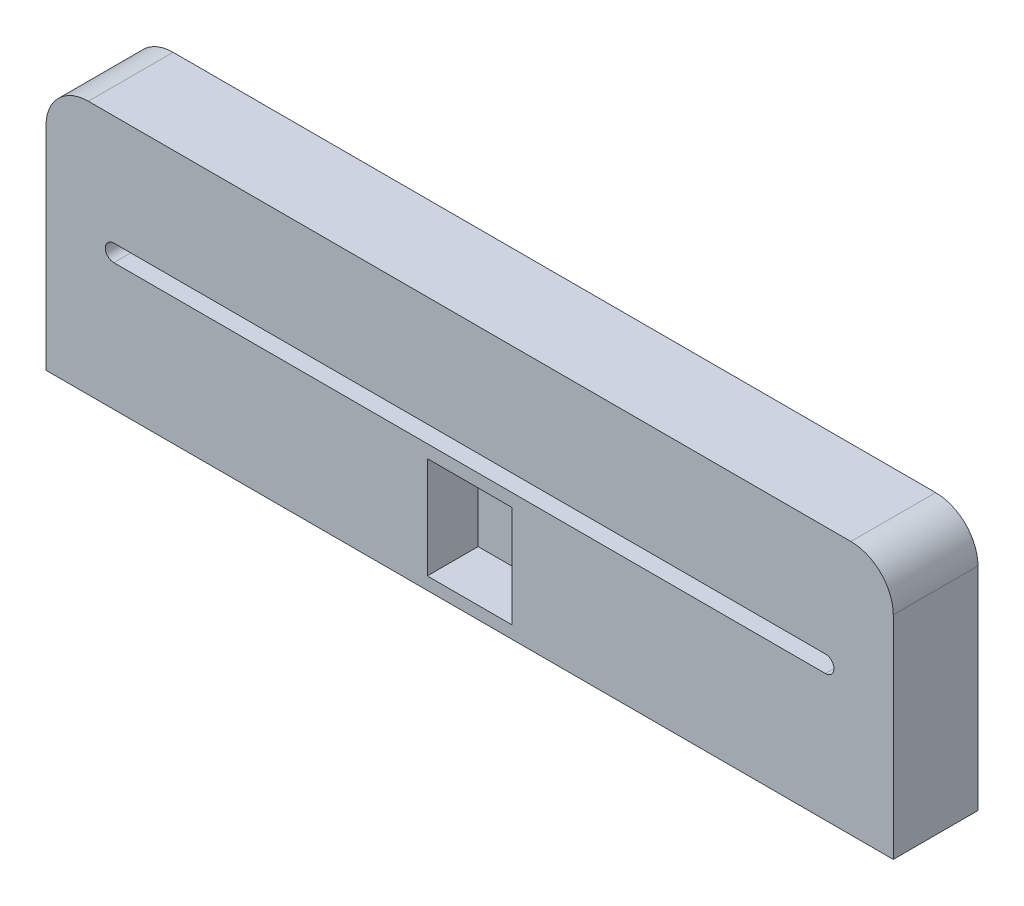
SolidWorks part; units mm, degrees
ref_plane "Alzado" through (0, 0, 0) normal (0, 0, 1) x (1, 0, 0)
ref_plane "Planta" through (0, 0, 0) normal (0, 1, 0) x (1, 0, 0)
ref_plane "Vista lateral" through (0, 0, 0) normal (1, 0, 0) x (0, 0, -1)
sketch "Croquis1" plane through (0, 0, 0) normal (0, 0, 1) x (1, 0, 0)
  line L0 (0, 0) -> (0, 7.5) construction
  line L1 (-25, 7.5) -> (25, 7.5)
  line L2 (-25, 7.5) -> (-25, -7.5)
  line L3 (-25, -7.5) -> (25, -7.5)
  line L4 (25, 7.5) -> (25, -7.5)
  line L5 (-25, 7.5) -> (25, -7.5) construction
  line L6 (-25, -7.5) -> (25, 7.5) construction
  line L12 (-22, 4.5) -> (22, 4.5)
  line L13 (-22, 4.5) -> (-22, -0.5)
  line L14 (-22, -0.5) -> (22, -0.5)
  line L15 (22, 4.5) -> (22, -0.5)
  line L16 (-22, 4.5) -> (22, -0.5) construction
  line L17 (-22, -0.5) -> (22, 4.5) construction
  point P0 (0, 0)
  point P6 (0, 0)
  point P9 (0, 2)
  dimension "D1" = 15
  dimension "D2" = 50
  dimension "D3" = 3
  dimension "D4" = 5
  dimension "D5" = 3
extrude "Saliente-Extruir1" add sketch "Croquis1" along normal blind 5 contours L15 L12 L13 L14 | L4 L1 L2 L3 L12 L15 L14 L13 region at (0, -0.8302, 0) region at (0, 2, 0)
extrude "Cortar-Extruir1" cut sketch "Croquis1<4>" along normal blind 2 contours L15 L12 L13 L14 region at (0, 2, 0)
sketch "Croquis1<4>" plane through (0, 0, 0) normal (0, 0, 1) x (1, 0, 0) same geometry as "Croquis1"
fillet "Redondeo1" radius 2.5 2 edges at (-25, 7.5, 2.5) (25, 7.5, 2.5)
sketch "Croquis2" plane through (0, 0, 2) normal (0, 0, -1) x (-1, 0, 0)
  line L0 (-22, 0.5) -> (22, 0.5) construction
  line L1 (-22, 4.5) -> (-22, -0.5) construction
  line L2 (22, 4.5) -> (22, -0.5) construction
  line L3 (22, -0.5) -> (-22, -0.5) construction
  line L4 (-21, 0.5) -> (21, 0.5) construction
  line L5 (-21, 1) -> (21, 1)
  line L6 (-21, 0) -> (21, 0)
  arc A0 (-21, 1) -> (-21, 0) centre (-21, 0.5) ccw
  arc A1 (21, 0) -> (21, 1) centre (21, 0.5) ccw
  point P10 (0, 0.5)
  dimension "D1" = 1
  dimension "D2" = 1
  dimension "D3" = 1
  dimension "D4" = 1
extrude "Cortar-Extruir2" cut sketch "Croquis2" against normal through all
sketch "Croquis3" plane through (0, 0, 5) normal (0, 0, 1) x (1, 0, 0)
  line L0 (0, 0) -> (0, -7.5) construction
  line L1 (-25, -7.5) -> (25, -7.5) construction
  line L3 (-2.5, -0.7601) -> (2.5, -0.7601)
  line L4 (-2.5, -0.7601) -> (-2.5, -6.7601)
  line L5 (-2.5, -6.7601) -> (2.5, -6.7601)
  line L6 (2.5, -0.7601) -> (2.5, -6.7601)
  line L7 (-2.5, -0.7601) -> (2.5, -6.7601) construction
  line L8 (-2.5, -6.7601) -> (2.5, -0.7601) construction
  point P5 (0, -3.7601)
  point P10 (0, -4.6819)
  point P11 (0, -3.7601)
  point P12 (0, 0)
  dimension "D1" = 5
  dimension "D2" = 6
extrude "Cortar-Extruir3" cut sketch "Croquis3" against normal blind 3
